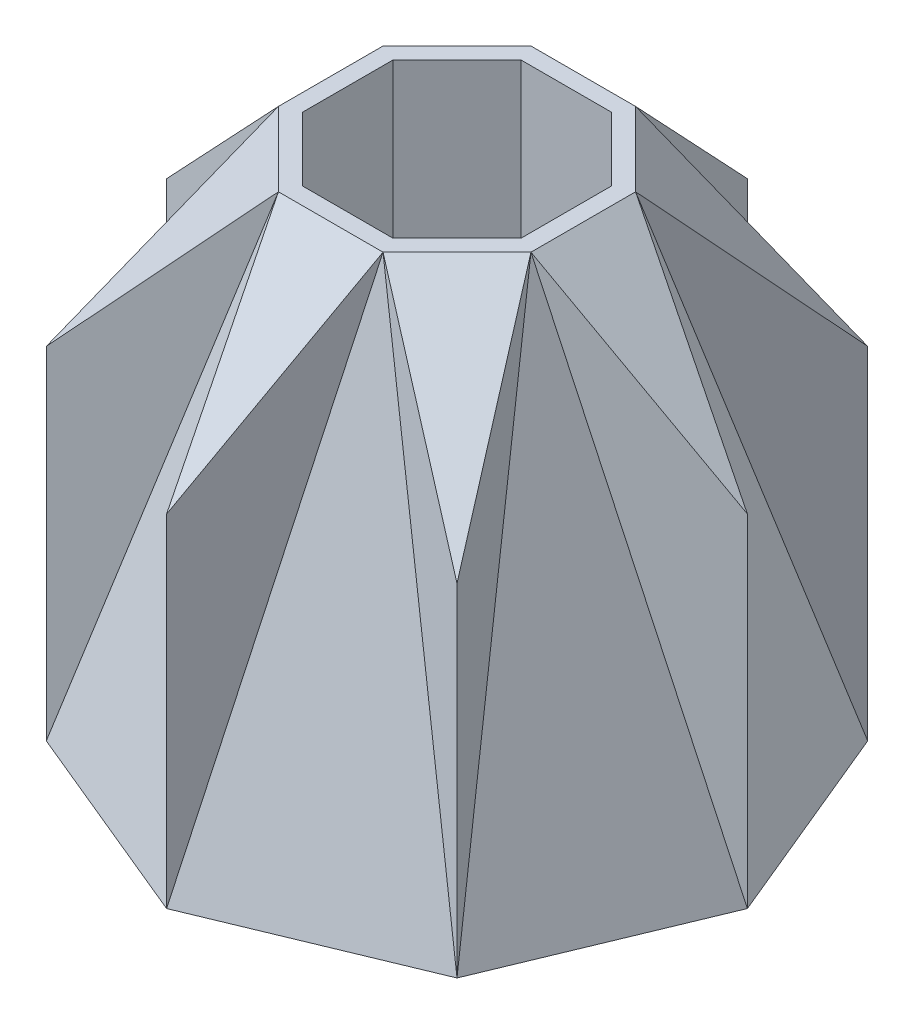
SolidWorks part; units mm, degrees
ref_plane "前视基准面" through (0, 0, 0) normal (0, 0, 1) x (1, 0, 0)
ref_plane "上视基准面" through (0, 0, 0) normal (0, 1, 0) x (1, 0, 0)
ref_plane "右视基准面" through (0, 0, 0) normal (1, 0, 0) x (0, 0, -1)
other "Configuration Table"
sketch "草图1" plane through (0, 0, 0) normal (0, 1, 0) x (1, 0, 0)
  line L0 (0, 0) -> (-102.8795, 0) construction
  line L1 (60.1041, -60.1041) -> (85, 0)
  line L2 (85, 0) -> (60.1041, 60.1041)
  line L3 (60.1041, 60.1041) -> (0, 85)
  line L4 (0, 85) -> (-60.1041, 60.1041)
  line L5 (-60.1041, 60.1041) -> (-85, 0)
  line L6 (-85, 0) -> (-60.1041, -60.1041)
  line L7 (-60.1041, -60.1041) -> (0, -85)
  line L8 (0, -85) -> (60.1041, -60.1041)
  line L9 (15.3073, -36.9552) -> (36.9552, -15.3073)
  line L10 (36.9552, -15.3073) -> (36.9552, 15.3073)
  line L11 (36.9552, 15.3073) -> (15.3073, 36.9552)
  line L12 (15.3073, 36.9552) -> (-15.3073, 36.9552)
  line L13 (-15.3073, 36.9552) -> (-36.9552, 15.3073)
  line L14 (-36.9552, 15.3073) -> (-36.9552, -15.3073)
  line L15 (-36.9552, -15.3073) -> (-15.3073, -36.9552)
  line L16 (-15.3073, -36.9552) -> (15.3073, -36.9552)
  line L17 (-13.2363, 31.9552) -> (-31.9552, 13.2363)
  line L18 (-31.9552, 13.2363) -> (-31.9552, -13.2363)
  line L19 (-31.9552, -13.2363) -> (-13.2363, -31.9552)
  line L20 (-13.2363, -31.9552) -> (13.2363, -31.9552)
  line L21 (13.2363, -31.9552) -> (31.9552, -13.2363)
  line L22 (31.9552, -13.2363) -> (31.9552, 13.2363)
  line L23 (31.9552, 13.2363) -> (13.2363, 31.9552)
  line L24 (13.2363, 31.9552) -> (-13.2363, 31.9552)
  circle A0 centre (0, 0) radius 78.5298 construction
  circle A1 centre (0, 0) radius 36.9552 construction
  point P1 (0, 0)
  dimension "D1" = 170
  dimension "D2" = 80
  dimension "D3" = 5
extrude "凸台-拉伸1" add sketch "草图1" along normal blind 150 contours L7 L8 L1 L2 L3 L4 L5 L6 L16 L15 L14 L13 L12 L11 L10 L9 region at (29.132, 0, 70.3309)
ref_plane "基准面1" through (-28.1919, 18.923, 68.0614) normal (-0.3707, 0.2488, 0.8948) x (0.9288, 0.0993, 0.3571)
ref_plane "基准面4" through (-28.1919, 18.923, 68.0614) normal (-0.3707, 0.2488, 0.8948) x (0.9288, 0.0993, 0.3571)
sketch "草图10" plane through (-28.1919, 18.923, 68.0614) normal (-0.3707, 0.2488, 0.8948) x (0.9288, 0.0993, 0.3571)
  line L1 (-61.5433, 158.2876) -> (88.4567, 158.2876)
  line L2 (-61.5433, 158.2876) -> (-61.5433, -43.6572)
  line L3 (-61.5433, -43.6572) -> (88.4567, -43.6572)
  line L4 (88.4567, 158.2876) -> (88.4567, -43.6572)
  line L5 (-61.5433, 158.2876) -> (88.4567, -43.6572) construction
  line L6 (-61.5433, -43.6572) -> (88.4567, 158.2876) construction
  point P0 (13.4567, 57.3152)
  dimension "D1" = 150
extrude "切除-拉伸9" cut sketch "草图10" along normal through all
ref_axis "基准轴5" through (0, 0, 0) along (0, 1, 0)
pattern_circular "阵列(圆周)6" count 8 over 360 about axis through (0, 0, 0) along (0, 1, 0) of "切除-拉伸9"
sketch "草图13" plane through (0, 0, 0) normal (0, 1, 0) x (1, 0, 0)
  line L0 (-36.9552, 15.3073) -> (-85, 0)
  line L1 (-85, 0) -> (-43.2957, 0) construction
  line L2 (-60.1041, 60.1041) -> (-85, 0) construction
  line L3 (-85, 0) -> (-36.9552, -15.3073)
  line L4 (-36.9552, -15.3073) -> (-36.9552, 15.3073)
extrude "凸台-拉伸6" add sketch "草图13" along normal through all
sketch "草图14" plane through (0, 0, 0) normal (0, 0, 1) x (1, 0, 0)
  line L0 (-36.9552, 150) -> (-85, 150)
  line L1 (-85, 150) -> (-85, 100)
  line L2 (-85, 150) -> (-85, 0) construction
  line L3 (-85, 100) -> (-36.9552, 150)
  line L4 (-85, 0) -> (-60.1041, 0) construction
  dimension "D1" = 100
extrude "切除-拉伸10" cut sketch "草图14" against normal up to next and the other way up to next
pattern_circular "阵列(圆周)7" count 8 over 360 about axis through (0, 0, 0) along (0, 1, 0) of "凸台-拉伸6", "切除-拉伸10"
extrude "凸台-拉伸7" add sketch "草图1<3>" along normal blind 150 contours L15 L16 L9 L10 L11 L12 L13 L14 L24 L23 L22 L21 L20 L19 L18 L17 region at (0, 0, 35.9099)
sketch "草图1<3>" plane through (0, 0, 0) normal (0, 1, 0) x (1, 0, 0) same geometry as "草图1"
